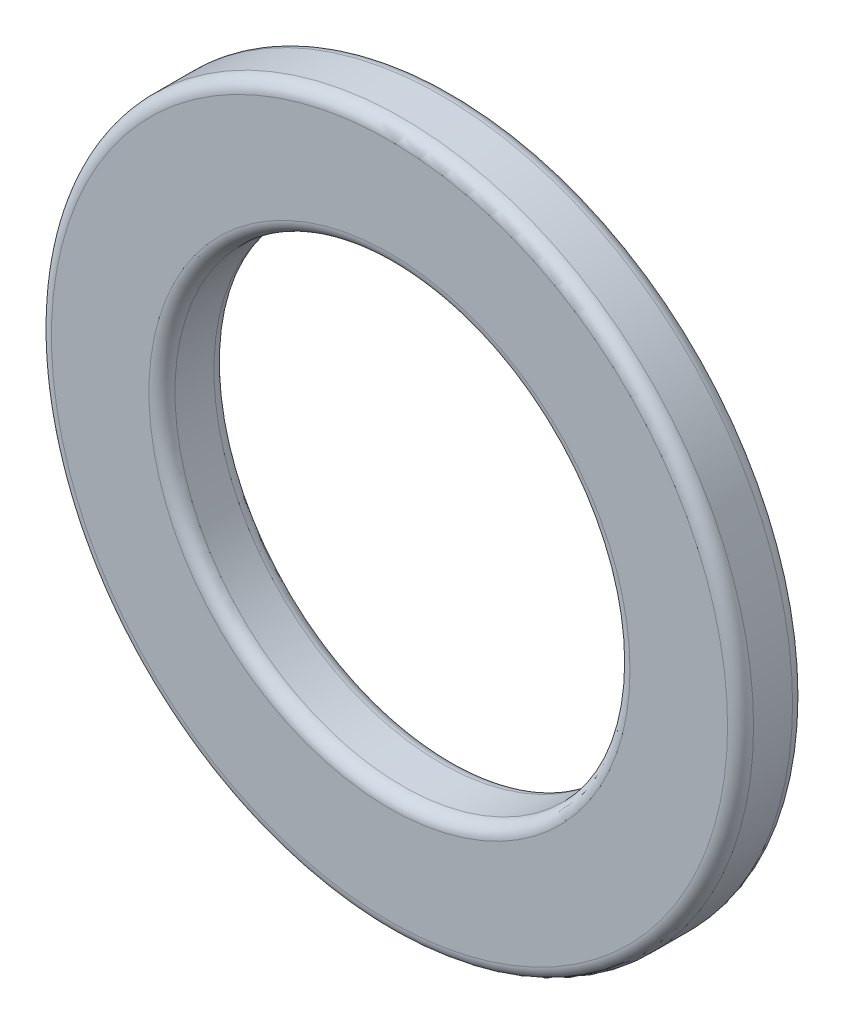
SolidWorks part; units mm, degrees
ref_plane "Front Plane" through (0, 0, 0) normal (0, 0, 1) x (1, 0, 0)
ref_plane "Top Plane" through (0, 0, 0) normal (0, 1, 0) x (1, 0, 0)
ref_plane "Right Plane" through (0, 0, 0) normal (1, 0, 0) x (0, 0, -1)
ref_axis "Z" through (0, 0, -88.49) along (0, 0, 1)
sketch "Sketch1" plane through (0, 0, 0) normal (0, 0, 1) x (1, 0, 0)
  circle A0 centre (0, 0) radius 5.4
  circle A1 centre (0, 0) radius 3.5
  dimension "D1" = 10.8
  dimension "D2" = 7
extrude "Boss-Extrude1" add sketch "Sketch1" along normal blind 1
fillet "Fillet1" radius 0.2 4 edges at (3.5, 0, 0) (3.5, 0, 1) (5.4, 0, 0) (5.4, 0, 1)
